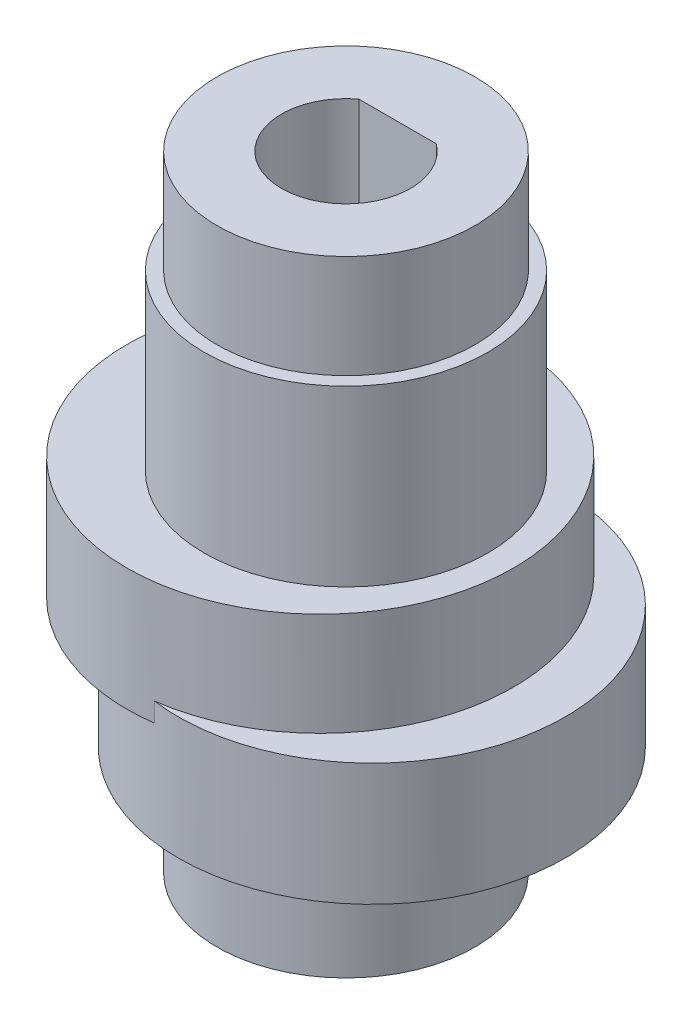
SolidWorks part; units mm, degrees
ref_plane "Front Plane" through (0, 0, 0) normal (0, 0, 1) x (1, 0, 0)
ref_plane "Top Plane" through (0, 0, 0) normal (0, 1, 0) x (1, 0, 0)
ref_plane "Right Plane" through (0, 0, 0) normal (1, 0, 0) x (0, 0, -1)
sketch "Sketch1" plane through (0, 0, 0) normal (0, 1, 0) x (1, 0, 0)
  line L0 (-1, 0) -> (1, 0) construction
  line L1 (-1.5, 2) -> (1.5, 2)
  circle A0 centre (1, 0) radius 7.5
  circle A1 centre (-1, 0) radius 7.5
  arc A2 (-1.5, 2) -> (1.5, 2) centre (0, 0) ccw
  dimension "D2" = 15
  dimension "D3" = 2.5
  dimension "D4" = 2
extrude "Boss-Extrude1" add sketch "Sketch1" along normal blind 4.74 contours A0 A1 | A0 A1 A2 L1 region at (4.4971, 0, -4.8071) region at (-6.6724, 0, 0)
extrude "Boss-Extrude2" add sketch "Sketch1<3>" along normal blind 0.74 contours A1 A0 region at (5.8236, 0, 5.516)
sketch "Sketch1<3>" plane through (0, 0, 0) normal (0, 1, 0) x (1, 0, 0) same geometry as "Sketch1"
extrude "Boss-Extrude3" add sketch "Sketch1<4>" against normal blind 4 contours A0 A1 A2 L1 | A1 A0 region at (5.8236, 0, 5.516) region at (4.4971, 0, -4.8071)
sketch "Sketch1<4>" plane through (0, 0, 0) normal (0, 1, 0) x (1, 0, 0) same geometry as "Sketch1"
sketch "Sketch2" plane through (0, -4, 0) normal (0, -1, 0) x (1, 0, 0)
  circle A0 centre (0, 0) radius 5.5
  circle A1 centre (0, 0) radius 5
  arc M1 (-1.5, -2) -> (1.5, -2) centre (0, 0) cw
  line M2 (1.5, -2) -> (-1.5, -2)
  dimension "D1" = 10
  dimension "D2" = 11
extrude "Boss-Extrude4" add sketch "Sketch2" along normal blind 4.74 contours A1 M2 M1 region at (-4.8586, -4, 0)
extrude "Boss-Extrude5" add sketch "Sketch2<3>" along normal blind 0.74
sketch "Sketch2<3>" plane through (0, -4, 0) normal (0, -1, 0) x (1, 0, 0) same geometry as "Sketch2"
extrude "Boss-Extrude6" add sketch "Sketch2<5>" against normal blind 15.48
sketch "Sketch2<5>" plane through (0, -4, 0) normal (0, -1, 0) x (1, 0, 0) same geometry as "Sketch2"
extrude "Boss-Extrude7" add sketch "Sketch2<6>" against normal blind 19.48 contours A1 M2 M1 region at (-4.8586, -4, 0)
sketch "Sketch2<6>" plane through (0, -4, 0) normal (0, -1, 0) x (1, 0, 0) same geometry as "Sketch2"
equation "\"bearing_21_OD\"= 21mm"
equation "\"pin_cirlce_diameter\"= 75mm"
equation "\"pin_diam\"= 6mm"
equation "\"gear_thickness\"= 4mm"
equation "\"ball_bearing_diam\"= 2.96mm"
equation "\"bearing_21_outer_clearance\"= 0mm'change this"
equation "\"bearing_15_OD\"= 15mm"
equation "\"bearing_15_outer_clearance\"= 0mm'change this"
equation "\"thrust_bearing_thickness\"= 5mm'measure this irl and change"
equation "\"eccentricity\"= 1mm"
equation "\"D1@Sketch1\"=\"eccentricity\"*2mm"
equation "\"D1@Boss-Extrude1\"=\"gear_thickness\"+\"ball_bearing_diam\"*0.25mm"
equation "\"D1@Boss-Extrude2\"=\"ball_bearing_diam\"*0.25mm"
equation "\"D1@Boss-Extrude3\"=\"gear_thickness\""
equation "\"bearing_21_ID\"=15mm"
equation "\"bearing_21_inner_clearance\"=0mm'change this"
equation "\"bearing_15_ID\"=10mm"
equation "\"bearing_15_inner_clearance\"= 0mm'change this"
equation "\"D2@Sketch1\"=\"bearing_21_ID\"-\"bearing_21_inner_clearance\""
equation "\"D1@Sketch2\"=\"bearing_15_ID\"-\"bearing_15_inner_clearance\""
equation "\"D2@Sketch2\"=\"bearing_15_ID\"-\"bearing_15_inner_clearance\"+1mm"
equation "\"D1@Boss-Extrude4\"=\"gear_thickness\"+\"ball_bearing_diam\"*0.25mm"
equation "\"D1@Boss-Extrude5\"=\"ball_bearing_diam\"*0.25mm"
equation "\"D1@Boss-Extrude6\"=\"gear_thickness\"*2+0.5*\"ball_bearing_diam\"+\"thrust_bearing_thickness\"+1mm"
equation "\"D1@Boss-Extrude7\"=\"gear_thickness\"*2+0.5*\"ball_bearing_diam\"+\"thrust_bearing_thickness\"+5mm"
